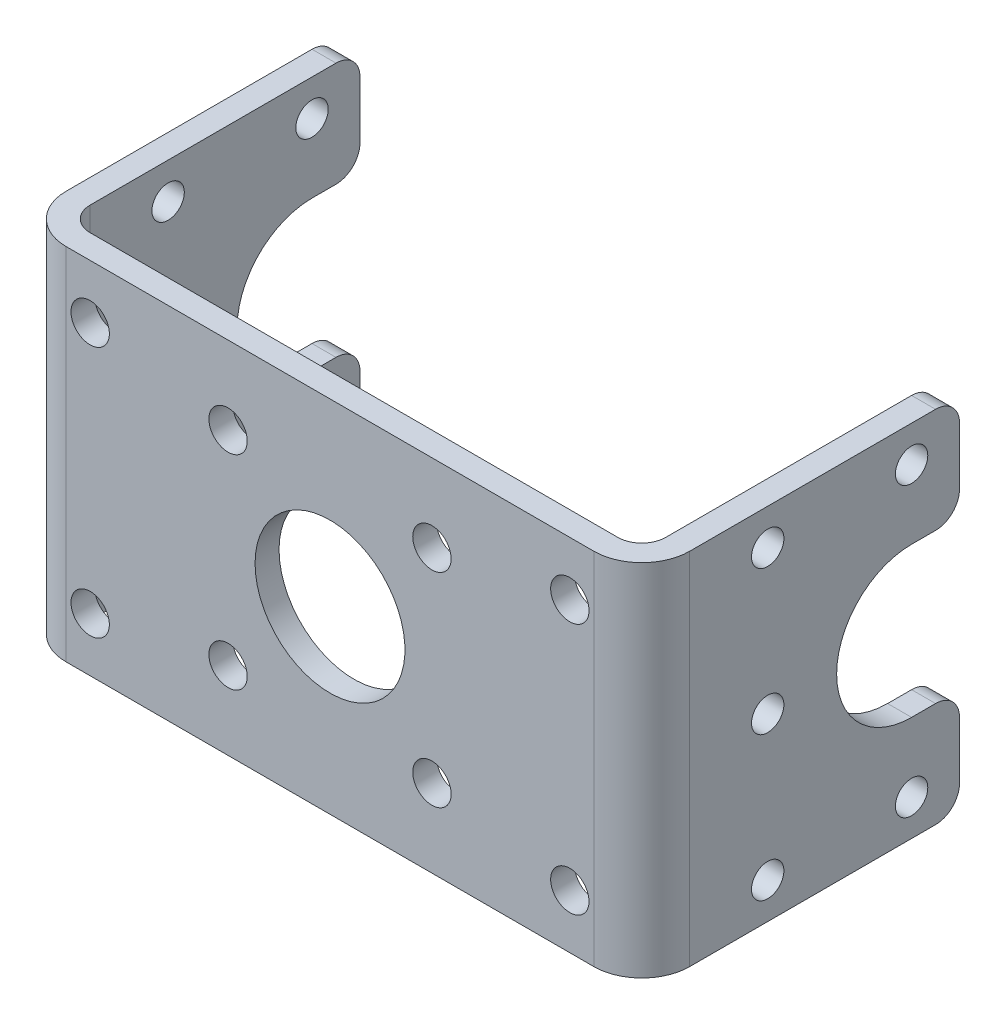
SolidWorks part; units mm, degrees
ref_plane "前视基准面" through (0, 0, 0) normal (0, 0, 1) x (1, 0, 0)
ref_plane "上视基准面" through (0, 0, 0) normal (0, 1, 0) x (1, 0, 0)
ref_plane "右视基准面" through (0, 0, 0) normal (1, 0, 0) x (0, 0, -1)
sketch "草图1" plane through (0, 0, 0) normal (0, 1, 0) x (1, 0, 0)
  line L0 (0, 0) -> (0, 77.3148) construction
  line L1 (0, 0) -> (22, 0)
  line L2 (26, 4) -> (26, 26.5)
  line L3 (0, 2) -> (22, 2)
  line L4 (24, 4) -> (24, 26.5)
  line L5 (26, 26.5) -> (24, 26.5)
  line L6 (-26, 26.5) -> (-24, 26.5)
  line L7 (-24, 4) -> (-24, 26.5)
  line L8 (0, 2) -> (-22, 2)
  line L9 (-26, 4) -> (-26, 26.5)
  line L10 (0, 0) -> (-22, 0)
  line L11 (0, 2) -> (24, 2) construction
  line L12 (24, 2) -> (24, 26.5) construction
  line L13 (0, 0) -> (26, 0) construction
  line L14 (26, 0) -> (26, 26.5) construction
  arc A0 (22, 2) -> (24, 4) centre (22, 4) ccw
  arc A1 (-22, 2) -> (-24, 4) centre (-22, 4) cw
  arc A2 (22, 0) -> (26, 4) centre (22, 4) ccw
  arc A3 (-22, 0) -> (-26, 4) centre (-22, 4) cw
  point P15 (24, 2)
  point P18 (-24, 2)
  point P22 (26, 0)
  point P25 (-26, 0)
  dimension "D4" = 2
  dimension "D5" = 4
  dimension "D2" = 48
  dimension "D3" = 26.5
  dimension "D1" = 2
extrude "凸台-拉伸1" add sketch "草图1" along normal mid plane 30
sketch "草图2" plane through (0, 0, -2) normal (0, 0, -1) x (-1, 0, 0)
  line L1 (-8.5, -8.5) -> (8.5, -8.5) construction
  line L2 (-8.5, -8.5) -> (-8.5, 8.5) construction
  line L3 (-8.5, 8.5) -> (8.5, 8.5) construction
  line L4 (8.5, -8.5) -> (8.5, 8.5) construction
  line L5 (-8.5, -8.5) -> (8.5, 8.5) construction
  line L6 (-8.5, 8.5) -> (8.5, -8.5) construction
  line L7 (-20, -10.5) -> (20, -10.5) construction
  line L8 (-20, -10.5) -> (-20, 10.5) construction
  line L9 (-20, 10.5) -> (20, 10.5) construction
  line L10 (20, -10.5) -> (20, 10.5) construction
  line L11 (-20, -10.5) -> (20, 10.5) construction
  line L12 (-20, 10.5) -> (20, -10.5) construction
  circle A0 centre (20, 10.5) radius 1.6
  circle A1 centre (8.5, 8.5) radius 1.6
  circle A2 centre (-8.5, 8.5) radius 1.6
  circle A3 centre (-20, 10.5) radius 1.6
  circle A4 centre (-20, -10.5) radius 1.6
  circle A5 centre (8.5, -8.5) radius 1.6
  circle A6 centre (-8.5, -8.5) radius 1.6
  circle A7 centre (20, -10.5) radius 1.6
  circle A8 centre (0, 0) radius 6.25
  point P0 (0, 0)
  point P6 (0, 0)
  dimension "D5" = 3.2
  dimension "D6" = 12.5
  dimension "D1" = 17
  dimension "D2" = 17
  dimension "D3" = 21
  dimension "D4" = 40
extrude "切除-拉伸1" cut sketch "草图2" against normal up to vertex (2 mm away) up to point (22, 15, 0)
sketch "草图3" plane through (0, 0, 0) normal (1, 0, 0) x (0, 0, -1)
  line L0 (0, 0) -> (22.5, 0) construction
  line L1 (22.5, 6.25) -> (26.5, 6.25)
  line L2 (26.5, 15) -> (26.5, -15) construction
  line L3 (22.5, 12) -> (22.5, -12) construction
  line L4 (22.5, 12) -> (10.5, 12) construction
  line L5 (22.5, -6.25) -> (26.5, -6.25)
  line L6 (26.5, 6.25) -> (26.5, -6.25)
  arc A0 (22.5, 6.25) -> (22.5, -6.25) centre (22.5, 0) ccw
  circle A1 centre (10.5, 12) radius 1.35
  circle A2 centre (22.5, 12) radius 1.35
  circle A3 centre (10.5, 0) radius 1.35
  circle A4 centre (22.5, -12) radius 1.35
  circle A5 centre (10.5, -12) radius 1.35
  point P10 (22.5, 0)
  dimension "D1" = 2.7
  dimension "D2" = 24
  dimension "D5" = 6.25
  dimension "D3" = 22.5
  dimension "D4" = 12
extrude "切除-拉伸2" cut sketch "草图3" against normal mid plane 63
fillet "圆角1" radius 2 8 edges at (25, -15, -26.5) (25, -6.25, -26.5) (25, 15, -26.5) (25, 6.25, -26.5) (-25, 15, -26.5) (-25, 6.25, -26.5) (-25, -6.25, -26.5) (-25, -15, -26.5)
